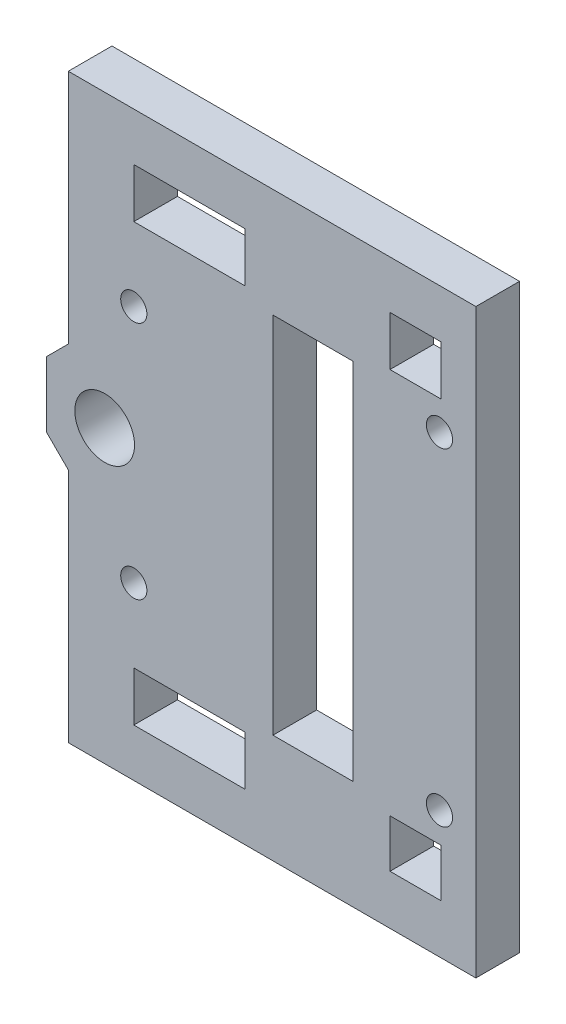
SolidWorks part; units mm, degrees
ref_plane "Plano frontal" through (0, 0, 0) normal (0, 0, 1) x (1, 0, 0)
ref_plane "Plano superior" through (0, 0, 0) normal (0, 1, 0) x (1, 0, 0)
ref_plane "Plano direito" through (0, 0, 0) normal (1, 0, 0) x (0, 0, -1)
sketch "Model" plane through (0, 0, 0) normal (0, 0, 1) x (1, 0, 0)
  line L0 (69.7947, 71.5746) -> (69.7947, 21.5746)
  line L1 (30.6773, 6.6246) -> (30.6773, 39.0855)
  line L2 (30.6773, 86.5246) -> (86.6773, 86.5246)
  line L3 (86.6773, 86.5246) -> (86.6773, 6.6246)
  line L4 (86.6773, 6.6246) -> (30.6773, 6.6246)
  line L5 (30.6773, 54.0637) -> (30.6773, 86.5246)
  line L6 (27.6773, 51.0637) -> (30.6773, 54.0637)
  line L7 (27.6773, 51.0637) -> (27.6773, 42.0855)
  line L8 (27.6773, 42.0855) -> (30.6773, 39.0855)
  line L9 (69.7947, 21.5746) -> (58.7947, 21.5746)
  line L10 (58.7947, 21.5746) -> (58.7947, 71.5746)
  line L11 (58.7947, 71.5746) -> (69.7947, 71.5746)
  line L12 (81.8773, 13.4246) -> (81.8773, 20.0246)
  line L13 (74.8773, 13.4246) -> (81.8773, 13.4246)
  line L14 (74.8773, 20.0246) -> (74.8773, 13.4246)
  line L15 (81.8773, 20.0246) -> (74.8773, 20.0246)
  line L16 (39.6773, 20.0246) -> (39.6773, 13.2246)
  line L17 (54.9895, 20.0246) -> (39.6773, 20.0246)
  line L18 (54.9895, 13.2246) -> (54.9895, 20.0246)
  line L19 (39.6773, 13.2246) -> (54.9895, 13.2246)
  line L20 (39.6773, 73.1246) -> (39.6773, 79.9246)
  line L21 (39.6773, 79.9246) -> (54.9895, 79.9246)
  line L22 (54.9895, 79.9246) -> (54.9895, 73.1246)
  line L23 (54.9895, 73.1246) -> (39.6773, 73.1246)
  line L24 (81.8773, 73.1246) -> (74.8773, 73.1246)
  line L25 (74.8773, 73.1246) -> (74.8773, 79.9246)
  line L26 (74.8773, 79.9246) -> (81.8773, 79.9246)
  line L27 (81.8773, 79.9246) -> (81.8773, 73.1246)
  circle A0 centre (81.6773, 24.0746) radius 1.8
  circle A1 centre (39.6773, 30.1246) radius 1.8
  circle A2 centre (35.6773, 46.5746) radius 4.1
  circle A3 centre (39.6773, 63.0246) radius 1.8
  circle A4 centre (81.6773, 69.0746) radius 1.8
extrude "Ressalto-extrusão1" add sketch "Model" along normal blind 6
